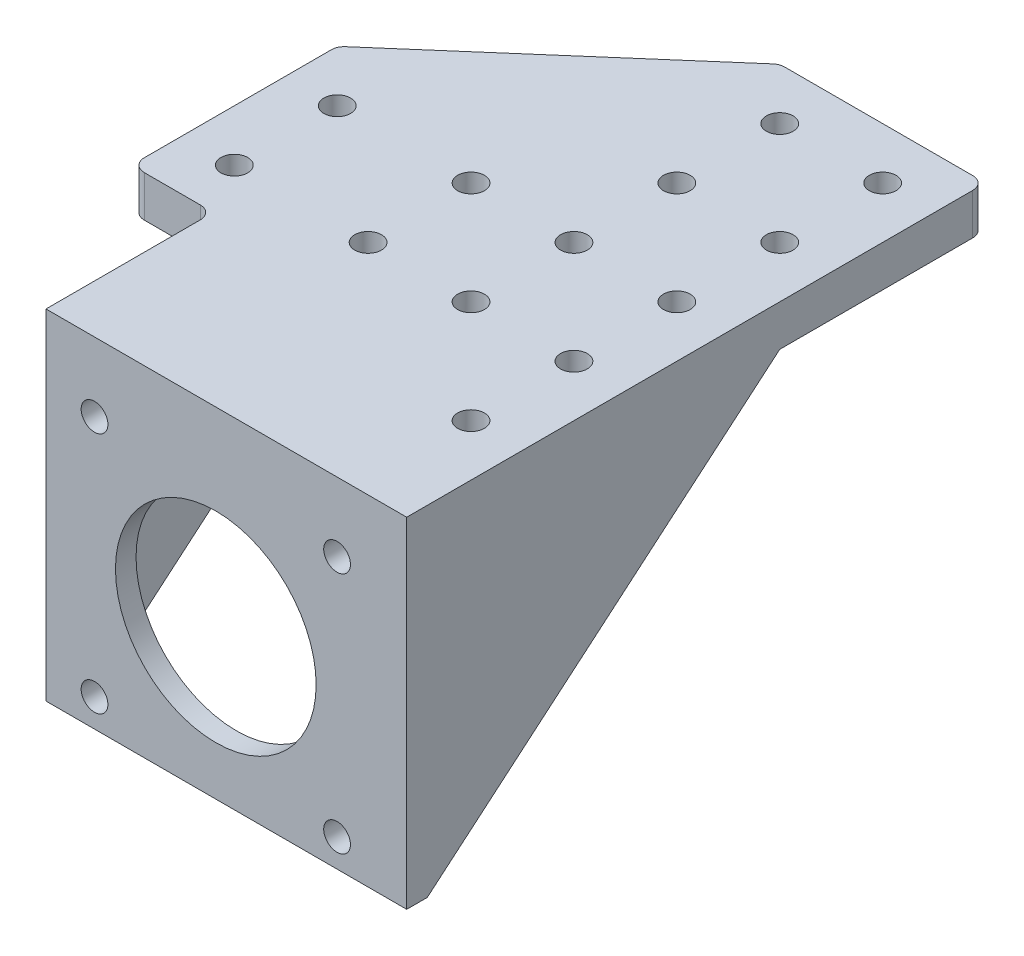
SolidWorks part; units mm, degrees
ref_plane "Спереди" through (0, 0, 0) normal (0, 0, 1) x (1, 0, 0)
ref_plane "Сверху" through (0, 0, 0) normal (0, 1, 0) x (1, 0, 0)
ref_plane "Справа" through (0, 0, 0) normal (1, 0, 0) x (0, 0, -1)
sketch "Эскиз1" plane through (0, 0, 0) normal (0, 0, 1) x (1, 0, 0)
  line L0 (29, 29) -> (29, -29) construction
  line L1 (-29, 29) -> (29, 29)
  line L2 (-29, 29) -> (-29, -29)
  line L3 (-29, -29) -> (29, -29)
  line L5 (29, 29) -> (33.1, 29)
  line L6 (33.1, 29) -> (33.1, -29)
  line L7 (33.1, -29) -> (29, -29)
  point P4 (-29, 0)
  dimension "D1" = 58
  dimension "D2" = 58
  dimension "D3" = 29
  dimension "D4" = 4.1
  dimension "D5" = 29
extrude "Бобышка-Вытянуть1" add sketch "Эскиз1" along normal blind 4
sketch "Эскиз6" plane through (0, 0, 4) normal (0, 0, 1) x (1, 0, 0)
  line L0 (-23.57, -23.57) -> (23.57, 23.57) construction
  circle A0 centre (0, 0) radius 19.5
  circle A1 centre (-23.57, 23.57) radius 2.6
  circle A2 centre (23.57, 23.57) radius 2.6
  circle A3 centre (-23.57, -23.57) radius 2.6
  circle A4 centre (23.57, -23.57) radius 2.6
  point P11 (0, 0)
  dimension "D1" = 39
  dimension "D2" = 5.2
  dimension "D3" = 5.2
  dimension "D4" = 5.2
  dimension "D5" = 5.2
  dimension "D7" = 47.14
  dimension "D6" = 47.14
extrude "Вырез-Вытянуть1" cut sketch "Эскиз6" against normal through all
sketch "Эскиз3" plane through (0, 29, 0) normal (0, 1, 0) x (1, 0, 0)
  line L0 (33.1, -4) -> (33.1, 0) construction
  line L1 (-29, -4) -> (37.1, -4)
  line L4 (37.1, -4) -> (37.1, 108.5)
  line L6 (37.1, 108.5) -> (-2.9, 108.5)
  line L7 (-48.9, 68.5) -> (-48.9, 28.5)
  line L9 (-48.9, 68.5) -> (-2.9, 108.5)
  line L10 (-29, -4) -> (-29, 0) construction
  line L11 (33.1, 0) -> (-29, 0) construction
  line L12 (57.4462, 28.5) -> (-49942.5538, 28.5) construction
  line L13 (-29, -4) -> (-29, 28.5)
  line L14 (-29, 28.5) -> (-48.9, 28.5)
  dimension "D1" = 40
  dimension "D2" = 86
  dimension "D3" = 4
  dimension "D4" = 80
  dimension "D5" = 40
  dimension "D7" = 28.5
extrude "Бобышка-Вытянуть2" add sketch "Эскиз3" along normal blind 8
sketch "Эскиз5" plane through (33.1, 0, 0) normal (1, 0, 0) x (0, 0, -1)
  line L7 (-4, -29) -> (-4, 37)
  line L13 (68.5, 29) -> (0, -29)
  line L21 (-4, -29) -> (0, -29) construction
  line L22 (0, -29) -> (0, 29) construction
  line L26 (0, -29) -> (-4, -29)
  line L27 (68.5, 29) -> (68.5, 37)
  line L28 (68.5, 37) -> (-4, 37)
  line L29 (-4, 29) -> (108.5, 29) construction
  dimension "D1" = 40.255
  dimension "D2" = 40
extrude "Бобышка-Вытянуть3" add sketch "Эскиз5" along normal blind 4
sketch "Эскиз10" plane through (-29, 0, 0) normal (-1, 0, 0) x (0, 0, 1)
  line L0 (4, -29) -> (0, -29)
  line L1 (4, -29) -> (4, 37)
  line L2 (4, 37) -> (-68.5, 37)
  line L4 (-68.5, 37) -> (-68.5, 29)
  line L5 (-68.5, 29) -> (0, -29)
  line L6 (-28.5, 29) -> (0, 29) construction
  dimension "D1" = 40.255
  dimension "D2" = 40
extrude "Бобышка-Вытянуть4" add sketch "Эскиз10" along normal blind 4
sketch "Эскиз8" plane through (0, 37, 0) normal (0, 1, 0) x (1, 0, 0)
  line L0 (37.1, 68.5) -> (37.1, 108.5) construction
  line L3 (37.1, 108.5) -> (-2.9, 108.5) construction
  circle A0 centre (27.1, 38.5) radius 2.6
  circle A1 centre (7.1, 38.5) radius 2.6
  circle A2 centre (7.1, 58.5) radius 2.6
  circle A3 centre (7.1, 78.5) radius 2.6
  circle A4 centre (7.1, 98.5) radius 2.6
  circle A5 centre (27.1, 58.5) radius 2.6
  circle A6 centre (27.1, 78.5) radius 2.6
  circle A7 centre (27.1, 98.5) radius 2.6
  circle A16 centre (-12.9, 58.5) radius 2.6
  circle A17 centre (-12.9, 38.5) radius 2.6
  circle A20 centre (-32.9, 38.5) radius 2.6 [skipped]
  circle A21 centre (-32.9, 58.5) radius 2.6 [skipped]
  circle A22 centre (-38.9, 58.5) radius 2.6
  circle A23 centre (-38.9, 38.5) radius 2.6
  circle A24 centre (27.1, 18.5) radius 2.6
  dimension "D1" = 5.2
  dimension "D2" = 10
  dimension "D3" = 10
  dimension "D7" = 2
  dimension "D8" = 20
  dimension "D9" = 26
  dimension "D10" = 20
  dimension "D11" = 20
  dimension "D12" = 20
  dimension "D13" = 20
  dimension "D14" = 20
  dimension "D15" = 20
  dimension "D16" = 90
  dimension "D17" = 20
  dimension "D4" = 2
  dimension "D5" = 4
  dimension "D6" = 3
extrude "Вырез-Вытянуть2" cut sketch "Эскиз8" against normal through all
sketch "Эскиз12" plane through (0, 29, 0) normal (0, -1, 0) x (1, 0, 0)
  circle A0 centre (27.1, -38.5) radius 5
  circle A1 centre (7.1, -38.5) radius 5
  circle A2 centre (-12.9, -38.5) radius 5
  circle A3 centre (7.1, -58.5) radius 5
  circle A4 centre (-12.9, -58.5) radius 5
  circle A5 centre (27.1, -58.5) radius 5
  circle A6 centre (27.1, -18.5) radius 5
  dimension "D1" = 10
  dimension "D2" = 3
  dimension "D3" = 2
  dimension "D4" = 2
extrude "Вырез-Вытянуть3" cut sketch "Эскиз12" against normal blind 3
sketch "Эскиз13" plane through (0, 29, 0) normal (0, -1, 0) x (1, 0, 0)
  circle A0 centre (-38.9, -38.5) radius 5
  circle A1 centre (-38.9, -58.5) radius 5
  circle A2 centre (27.1, -78.5) radius 5
  circle A3 centre (7.1, -78.5) radius 5
  circle A4 centre (7.1, -98.5) radius 5
  circle A5 centre (27.1, -98.5) radius 5
  dimension "D1" = 10
  dimension "D2" = 10
  dimension "D3" = 10
extrude "Вырез-Вытянуть4" cut sketch "Эскиз13" against normal blind 0.2
fillet "Скругление1" radius 2.5 5 edges at (-2.9, 33, -108.5) (-48.9, 33, -68.5) (-48.9, 33, -28.5) (37.1, 33, -108.5) (-33, 33, -28.5)
chamfer "Фаска2" distance 3 angle 45 2 edges at (33.1, 29, -34.25) (-29, 29, -34.25)
mirror "Зеркальное отражение2" [suppressed] about plane through (0, 0, 0) normal (1, 0, 0) of bodies 115 108
delete or keep bodies "Тело-Удалить/Сохранить 1" [suppressed] type delete bodies bodies 115
